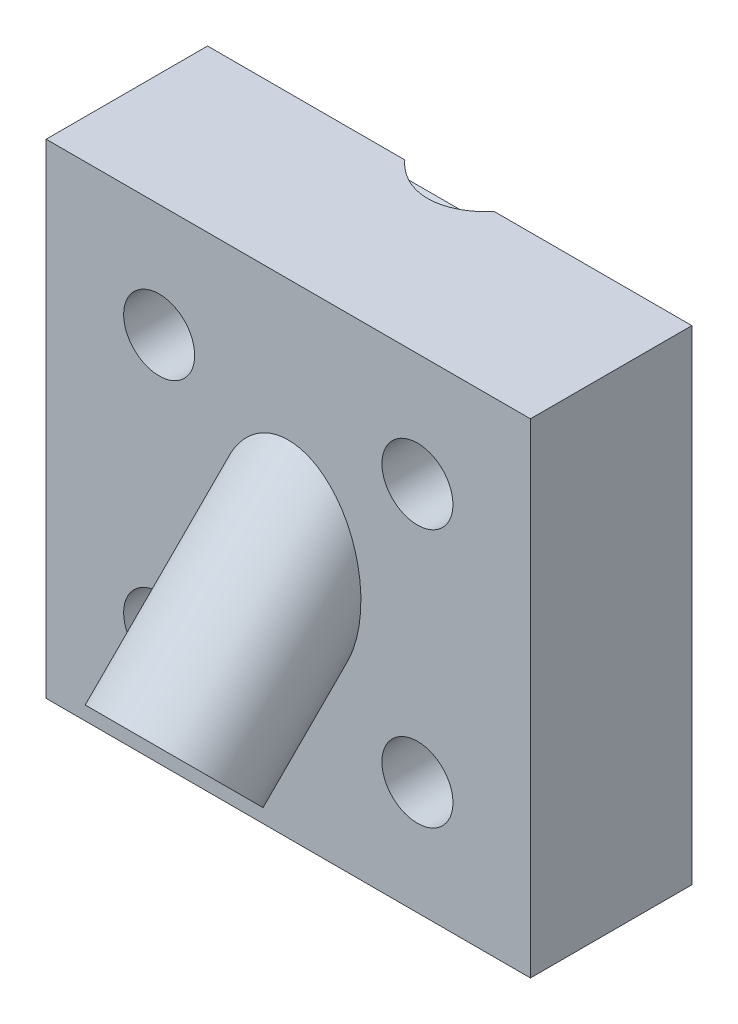
SolidWorks part; units mm, degrees
ref_plane "前视基准面" through (0, 0, 0) normal (0, 0, 1) x (1, 0, 0)
ref_plane "上视基准面" through (0, 0, 0) normal (0, 1, 0) x (1, 0, 0)
ref_plane "右视基准面" through (0, 0, 0) normal (1, 0, 0) x (0, 0, -1)
sketch "Sketch1" plane through (0, 0, 0) normal (0, 0, 1) x (1, 0, 0)
  line L0 (0, -7.5) -> (7.5, -7.5) construction
  line L1 (0, 0) -> (15, 0)
  line L2 (0, 0) -> (0, -15)
  line L3 (0, -15) -> (15, -15)
  line L4 (15, 0) -> (15, -15)
  line L6 (3.5, -11.5) -> (11.5, -11.5) construction
  line L7 (3.5, -11.5) -> (3.5, -3.5) construction
  line L8 (3.5, -3.5) -> (11.5, -3.5) construction
  line L9 (11.5, -11.5) -> (11.5, -3.5) construction
  line L10 (3.5, -11.5) -> (11.5, -3.5) construction
  line L11 (3.5, -3.5) -> (11.5, -11.5) construction
  circle A0 centre (3.5, -3.5) radius 1.1
  circle A1 centre (11.5, -3.5) radius 1.1
  circle A2 centre (11.5, -11.5) radius 1.1
  circle A3 centre (3.5, -11.5) radius 1.1
  dimension "D6" = 2.2
  dimension "D7" = 2.2
  dimension "D8" = 2.2
  dimension "D9" = 2.2
  dimension "D1" = 15
  dimension "D2" = 15
  dimension "D3" = 7.5
  dimension "D4" = 8
  dimension "D5" = 8
extrude "Extrude1" add sketch "Sketch1" along normal blind 4
sketch "Sketch2" plane through (0, 0, 4) normal (0, 0, 1) x (1, 0, 0)
  line L0 (0, -7.5) -> (15, -7.5) construction
  line L1 (0, 0) -> (0, -15) construction
  line L2 (15, -15) -> (15, 0) construction
ref_plane "Plane1" through (0, -5.75, 5.75) normal (0, -0.7071, 0.7071) x (1, 0, 0)
sketch "Sketch3" plane through (0, -5.75, 5.75) normal (0, -0.7071, 0.7071) x (1, 0, 0)
  line L0 (0, -2.4749) -> (15, -2.4749) construction
  circle A0 centre (7.5, -2.4749) radius 2
  dimension "D1" = 4
extrude "Extrude2" add sketch "Sketch3" along normal blind 60 and the other way blind 4
sketch "Sketch4" plane through (0, -48.1764, 48.1764) normal (0, -0.7071, 0.7071) x (1, 0, 0)
  line L0 (0, -2.4749) -> (15, -2.4749) construction
  circle A0 centre (7.5, -2.4749) radius 1.75
  dimension "D1" = 3.5
extrude "Extrude3" add sketch "Sketch4" along normal blind 3
sketch "Sketch5" plane through (0, -50.2977, 50.2977) normal (0, -0.7071, 0.7071) x (-1, 0, 0)
  line L0 (0, 2.4749) -> (-15, 2.4749) construction
  circle A0 centre (-7.5, 2.4749) radius 2
  dimension "D1" = 4
extrude "Extrude4" add sketch "Sketch5" along normal blind 3
sketch "Sketch9" plane through (0, 0, 0) normal (1, 0, 0) x (0, 0, -1)
  line L0 (-47.6638, -48.689) -> (-49.7852, -50.8103) construction
  line L1 (-47.8406, -48.5122) -> (-45.0122, -51.3406) construction
  line L2 (-47.1335, -53.4619) -> (-49.9619, -50.6335) construction
  line L3 (-47.3103, -53.2852) -> (-45.189, -51.1638) construction
  line L4 (-47.6638, -48.689) -> (-49.7852, -50.8103)
  line L5 (-47.8406, -48.5122) -> (-45.0122, -51.3406)
  line L6 (-47.1335, -53.4619) -> (-49.9619, -50.6335)
  line L7 (-47.3103, -53.2852) -> (-45.189, -51.1638)
  line L8 (-48.5477, -52.0477) -> (-46.4264, -49.9264) construction
  line L9 (-48.7245, -49.7496) -> (-47.4871, -50.9871) construction
  circle A0 centre (-47.4871, -50.9871) radius 0.5
  dimension "D1" = 1
extrude "Extrude8" cut sketch "Sketch9" along normal blind 63 contours A0
sketch "草图1" plane through (15, 0, 0) normal (1, 0, 0) x (0, 0, -1)
  line L1 (-4, 0) -> (-67.2097, 0)
  line L2 (-4, 0) -> (-4, -58.1971)
  line L3 (-4, -58.1971) -> (-67.2097, -58.1971)
  line L4 (-67.2097, 0) -> (-67.2097, -58.1971)
sketch "草图4" plane through (0, 0, 0) normal (0, 0, -1) x (-1, 0, 0)
  line L0 (0, 0) -> (0, -15) construction
  line L1 (0, -15) -> (-15, -15) construction
  line L2 (-15, 0) -> (-15, -58.1971) construction
  line L3 (-15, 0) -> (0, 0) construction
  line L4 (0, 0) -> (0, -15)
  line L5 (0, -15) -> (-15, -15)
  line L6 (-15, 0) -> (-15, -15)
  line L7 (-15, 0) -> (0, 0)
  circle A0 centre (-3.5, -3.5) radius 1.1 construction
  circle A1 centre (-11.5, -3.5) radius 1.1 construction
  circle A2 centre (-11.5, -11.5) radius 1.1 construction
  circle A3 centre (-3.5, -11.5) radius 1.1 construction
  circle A4 centre (-3.5, -3.5) radius 1.1
  circle A5 centre (-11.5, -3.5) radius 1.1
  circle A6 centre (-11.5, -11.5) radius 1.1
  circle A7 centre (-3.5, -11.5) radius 1.1
extrude "凸台-拉伸1" add sketch "草图4" along normal blind 1
sketch "草图3" plane through (0, -52.419, 52.419) normal (0, -0.7071, 0.7071) x (1, 0, 0)
  circle A0 centre (7.5, -2.4749) radius 1.5
  dimension "D1" = 3
extrude "切除-拉伸2" cut sketch "草图3" against normal blind 104
sketch "草图5" plane through (15, 0, 0) normal (1, 0, 0) x (0, 0, -1)
  line L1 (-4, 0) -> (-67.2097, 0)
  line L2 (-4, 0) -> (-4, -58.1971)
  line L3 (-4, -58.1971) -> (-67.2097, -58.1971)
  line L4 (-67.2097, 0) -> (-67.2097, -58.1971)
extrude "切除-拉伸3" cut sketch "草图5" against normal blind 40
sketch "草图6" plane through (0, -5.75, 5.75) normal (0, -0.7071, 0.7071) x (1, 0, 0)
  line L0 (0, -2.4749) -> (15, -2.4749) construction
  circle A0 centre (7.5, -2.4749) radius 1.5
  circle A1 centre (7.5, -2.4749) radius 2.25
  dimension "D1" = 3
  dimension "D2" = 4.5
extrude "凸台-拉伸2" add sketch "草图6" along normal blind 5 and the other way blind 10
sketch "草图7" plane through (0, 1.3211, -1.3211) normal (0, 0.7071, -0.7071) x (1, 0, 0)
  circle A0 centre (7.5, 2.4749) radius 2.25
extrude "切除-拉伸4" cut sketch "草图7" against normal blind 1.5
